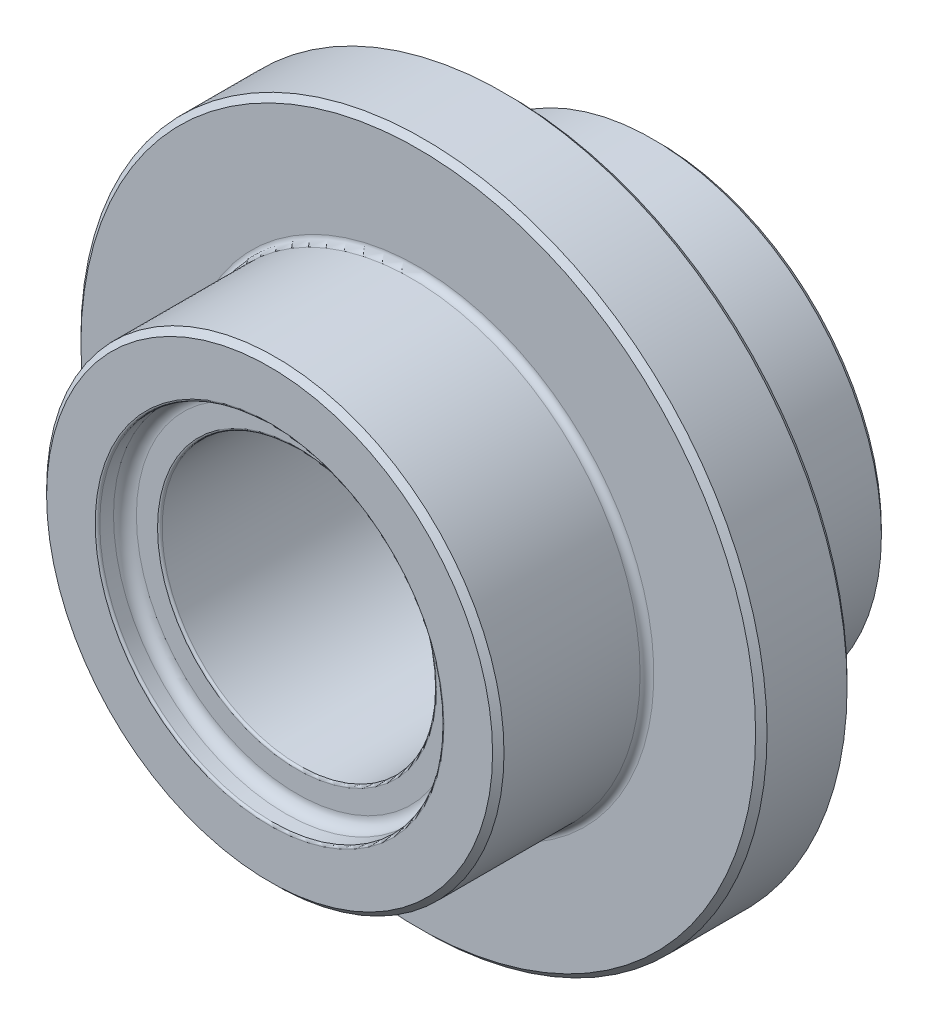
SolidWorks part; units mm, degrees
material "Plain Carbon Steel"
ref_plane "Front" through (0, 0, 0) normal (0, 0, 1) x (1, 0, 0)
ref_plane "Top" through (0, 0, 0) normal (0, 1, 0) x (1, 0, 0)
ref_plane "Right" through (0, 0, 0) normal (1, 0, 0) x (0, 0, -1)
ref_axis "Axis1" through (-84.4107, 0, 0) along (1, 0, 0)
ref_axis "Axis2" through (0, 64.3378, 0) along (0, -1, 0)
ref_axis "Axis3" through (0, 0, -102.329) along (0, 0, 1)
sketch "Sketch1" plane through (0, 0, 0) normal (0, 0, 1) x (1, 0, 0)
  circle A0 centre (0, 0) radius 20
  dimension "D1" = 40
extrude "Boss-Extrude1" add sketch "Sketch1" along normal blind 13
sketch "Sketch2" plane through (0, 0, 0) normal (0, 0, -1) x (-1, 0, 0)
  circle A0 centre (0, 0) radius 30
  dimension "D1" = 60
extrude "Boss-Extrude2" add sketch "Sketch2" along normal blind 8
sketch "Sketch3" plane through (0, 0, -8) normal (0, 0, -1) x (-1, 0, 0)
  circle A0 centre (0, 0) radius 20
  dimension "D1" = 40
extrude "Boss-Extrude3" add sketch "Sketch3" along normal blind 13
sketch "Sketch4" plane through (0, 0, 13) normal (0, 0, 1) x (1, 0, 0)
  circle A0 centre (0, 0) radius 12
  dimension "D1" = 24
extrude "Cut-Extrude1" cut sketch "Sketch4" against normal up to next
sketch "Sketch5" plane through (0, 0, 13) normal (0, 0, 1) x (1, 0, 0)
  circle A0 centre (0, 0) radius 15.05
  dimension "D1" = 30.1
extrude "Cut-Extrude2" cut sketch "Sketch5" against normal blind 2.4
chamfer "Chamfer1" distance 0.5 angle 45 5 edges at (-12, 0, -21) (-20, 0, -21) (-30, 0, -8) (-30, 0, 0) (20, 0, 13)
fillet "Fillet1" radius 0.6 2 edges at (20, 0, 0) (-20, 0, -8)
fillet "Fillet2" radius 0.2 2 edges at (15.05, 0, 13) (12, 0, 10.6)
fillet "Fillet3" radius 1 1 edges at (15.05, 0, 10.6)
ref_plane "back" through (0, 0, 13) normal (0, 0, 1) x (1, 0, 0)
ref_plane "Plane2" through (0, 0, -21) normal (0, 0, -1) x (-1, 0, 0)
ref_plane "Plane3" through (0, 0, -8) normal (0, 0, -1) x (-1, 0, 0)
ref_plane "Plane4" through (0, 0, 0) normal (0, 0, 1) x (1, 0, 0)
